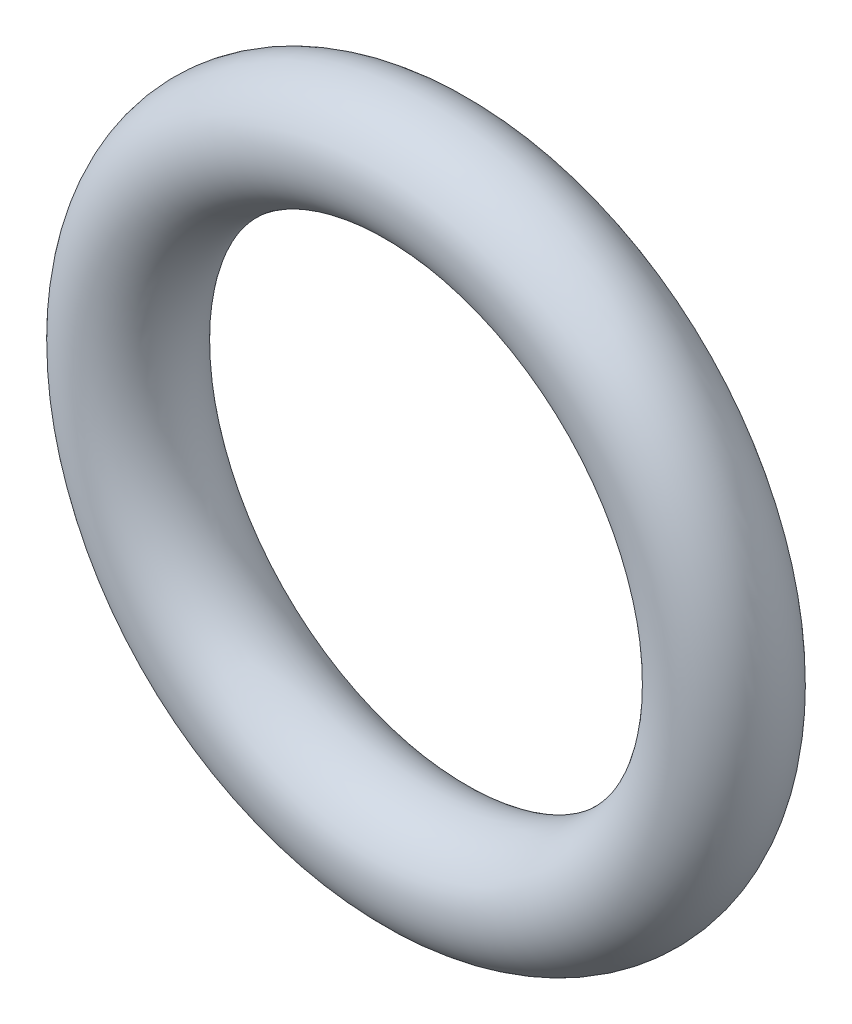
SolidWorks part; units mm, degrees
ref_plane "Front" through (0, 0, 0) normal (0, 0, 1) x (1, 0, 0)
ref_plane "Top" through (0, 0, 0) normal (0, 1, 0) x (1, 0, 0)
ref_plane "Right" through (0, 0, 0) normal (1, 0, 0) x (0, 0, -1)
sketch "Sketch1" plane through (0, 0, 0) normal (0, 0, 1) x (1, 0, 0)
  circle A0 centre (0, 0) radius 3.75
  dimension "d1" = 7.5
sketch "Sketch2" plane through (0, 0, 0) normal (0, 1, 0) x (1, 0, 0)
  circle A0 centre (-4.65, 0) radius 0.9
  point P2 (-3.75, 0)
  dimension "d2" = 1.8
sweep "Sweep1" add profiles "Sketch2" path "Sketch1"
ref_axis "Axis1" through (0, 0, -4.8575) along (0, 0, 1)
